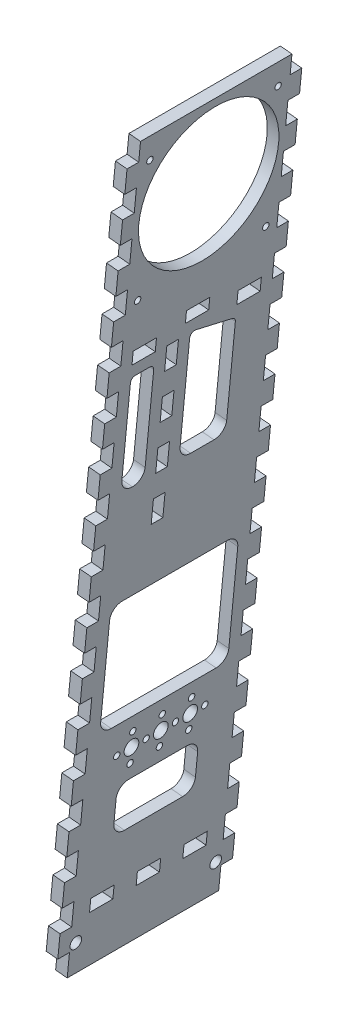
SolidWorks part; units mm, degrees
ref_plane "Front Plane" through (0, 0, 0) normal (0, 0, 1) x (1, 0, 0)
ref_plane "Top Plane" through (0, 0, 0) normal (0, 1, 0) x (1, 0, 0)
ref_plane "Right Plane" through (0, 0, 0) normal (1, 0, 0) x (0, 0, -1)
sketch "Sketch1" plane through (0, 0, 0) normal (0, 0, 1) x (1, 0, 0)
  line L0 (0, 0) -> (40.3547, 419.1) construction
  line L1 (40.3547, 419.1) -> (159.2585, 419.1) construction
  line L2 (159.2585, 419.1) -> (159.2585, 0) construction
  line L3 (159.2585, 0) -> (0, 0) construction
  line L4 (159.2585, -1000) -> (159.2585, 49000) construction
  line L5 (2.0164, 20.9415) -> (40.3547, 419.1) construction
  line L6 (2.0164, 20.9415) -> (41.8323, 17.1077) construction
  line L7 (40.3547, 419.1) -> (80.1706, 415.2662) construction
  line L8 (41.8323, 17.1077) -> (80.1706, 415.2662) construction
  line L9 (64.0085, -1000) -> (64.0085, 49000) construction
  line L10 (-42.7214, 317.5) -> (-118.5706, 324.8034) construction
  line L11 (-20.0013, 414.3375) -> (40.196, 414.3375) construction
  line L12 (-1162.1335, 304.8) -> (48837.8665, 304.8) construction
  line L13 (-120.1415, 292.1) -> (-43.9415, 292.1) construction
  line L14 (-118.5706, 324.8034) -> (-43.9415, 292.1) construction
  line L15 (-42.7214, 317.5) -> (-120.1415, 292.1) construction
  line L16 (40.196, 338.1375) -> (-20.0013, 338.1375) construction
  line L17 (-128.0517, 325.7164) -> (29.8985, 310.5075)
  line L18 (-128.0517, 325.7164) -> (-127.4431, 332.0371)
  line L19 (-127.4431, 332.0371) -> (40.3547, 419.1)
  line L20 (40.3547, 419.1) -> (108.4585, 419.1)
  line L21 (108.4585, 419.1) -> (108.4585, 0) construction
  line L22 (29.8985, 310.5075) -> (0.4102, 4.2603)
  line L23 (0.4102, 4.2603) -> (44.6556, 0)
  line L24 (44.6556, 0) -> (108.4585, 0)
  line L25 (108.4585, 419.1) -> (159.2585, 311.15)
  line L26 (159.2585, 311.15) -> (159.2585, 304.8)
  line L27 (159.2585, 304.8) -> (108.4585, 280.8941)
  line L28 (108.4585, 280.8941) -> (108.4585, 0)
  line L29 (29.9603, 304.8) -> (29.9603, 311.15) construction
  line L30 (108.4585, 38.1) -> (3.0572, 38.1)
  line L31 (108.4585, 38.1) -> (108.4585, 31.75)
  line L32 (108.4585, 31.75) -> (3.0572, 31.75)
  line L33 (3.0572, 38.1) -> (3.0572, 31.75)
  line L34 (29.9603, 311.15) -> (36.3397, 311.15) construction
  arc A0 (-118.5706, 324.8034) -> (-20.0013, 414.3375) centre (-20.0013, 315.3123) cw construction
  arc A1 (73.5335, 304.8) -> (40.196, 338.1375) centre (40.196, 304.8) ccw construction
  arc A2 (149.7335, 304.8) -> (40.196, 414.3375) centre (40.196, 304.8) ccw construction
  arc A3 (-42.7214, 317.5) -> (-20.0013, 338.1375) centre (-20.0013, 315.3123) cw construction
  point P7 (57.6585, 400.05)
  point P10 (46.2594, 414.1696)
  point P17 (149.7335, 304.8)
  point P18 (73.5335, 304.8)
  point P43 (10.048, 38.1)
  point P44 (19.5659, 203.2)
  dimension "D9" = 9.525
  dimension "D14" = 25.4
  dimension "D1" = 419.1
  dimension "D2" = 101.6
  dimension "D3" = 19.05
  dimension "D4" = 19.05
  dimension "D5" = 84.5
  dimension "D6" = 40
  dimension "D7" = 400
  dimension "D8" = 95.25
  dimension "D10" = 9.525
  dimension "D11" = 114.3
  dimension "D12" = 76.2
  dimension "D13" = 9.525
  dimension "D15" = 127
  dimension "D16" = 9.525
  dimension "D17" = 203.2
  dimension "D18" = 6.35
  dimension "D19" = 50.8
  dimension "D20" = 44.45
  dimension "D21" = 6.35
  dimension "D22" = 6.35
  dimension "D23" = 31.75
  dimension "D24" = 6.35
  dimension "D25" = 6.35
  dimension "D26" = 101.6
  dimension "D27" = 6.35
  dimension "D28" = 6.35
sketch "Sketch2" plane through (0, 0, 0) normal (0, 0, 1) x (1, 0, 0)
  line L0 (6.731, 3.6517) -> (0.4102, 4.2603)
  line L1 (6.731, 3.6517) -> (46.6755, 418.4914)
  line L2 (0.4102, 4.2603) -> (40.3547, 419.1)
  line L3 (46.6755, 418.4914) -> (40.3547, 419.1)
  line L4 (0.4102, 4.2603) -> (44.6556, 0) construction
  line L5 (40.3547, 419.1) -> (108.4585, 419.1) construction
  dimension "D2" = 6.35
extrude "Boss-Extrude1" add sketch "Sketch2" along normal blind 95.25
sketch "Sketch3" plane through (0, 0, 0) normal (-0.9954, 0.0958, 0) x (0, 0, 1)
  line L0 (47.625, 378.199) -> (47.625, 421.0384) construction
  line L1 (95.25, 421.0384) -> (0, 421.0384) construction
  line L2 (47.625, 416.6966) -> (0, 416.6966) construction
  line L3 (0, 421.0384) -> (0, 4.28) construction
  line L4 (47.625, 339.7014) -> (0, 339.7014) construction
  line L5 (0, 0) -> (0, 421.0384) construction
  ellipse E0 centre (47.625, 378.199) end of major axis (47.625, 416.6966) minor radius 38.1
  dimension "D1" = 76.2
extrude "Cut-Extrude1" cut sketch "Sketch3" against normal through all
sketch "Sketch4" plane through (0, 0, 0) normal (-0.9954, 0.0958, 0) x (0, 0, 1)
  line L0 (95.25, 4.28) -> (0, 4.28) construction
  line L1 (9.525, -11.595) -> (85.725, -11.595) construction
  line L2 (9.525, -11.595) -> (9.525, 20.155) construction
  line L3 (9.525, 20.155) -> (85.725, 20.155) construction
  line L4 (85.725, -11.595) -> (85.725, 20.155) construction
  line L5 (9.525, -11.595) -> (85.725, 20.155) construction
  line L6 (9.525, 20.155) -> (85.725, -11.595) construction
  line L7 (0, 421.0384) -> (0, 4.28) construction
  circle A0 centre (9.525, 20.155) radius 3.175
  circle A1 centre (85.725, 20.155) radius 3.175
  point P0 (47.625, 4.28)
  dimension "D3" = 6.35
  dimension "D1" = 9.525
  dimension "D2" = 15.875
extrude "Cut-Extrude2" cut sketch "Sketch4" against normal through all
sketch "Sketch5" plane through (0, 0, 0) normal (-0.9954, 0.0958, 0) x (0, 0, 1)
  line L0 (95.25, 4.28) -> (0, 4.28) construction
  line L1 (47.625, -995.72) -> (47.625, 49004.28) construction
  line L2 (63.625, 105.88) -> (63.625, 113.88) construction
  circle A0 centre (63.625, 105.88) radius 4
  circle A1 centre (63.625, 113.88) radius 1.75
  circle A2 centre (71.625, 105.88) radius 1.75
  circle A3 centre (63.625, 97.88) radius 1.75
  circle A4 centre (55.625, 105.88) radius 1.75
  point P7 (47.625, 4.28)
  point P18 (63.625, 105.88)
  dimension "D2" = 8
  dimension "D5" = 3.5
  dimension "D1" = 101.6
  dimension "D3" = 16
  dimension "D4" = 8
  dimension "D6" = 4
extrude "Cut-Extrude3" cut sketch "Sketch5" against normal through all
pattern_linear "LPattern1" count 3 spacing 16 along (0, 0, -1) of "Cut-Extrude3"
sketch "Sketch6" plane through (0, 0, 0) normal (-0.9954, 0.0958, 0) x (0, 0, 1)
  line L0 (0, 421.0384) -> (0, 4.28) construction
  line L1 (12.7, 185.38) -> (82.55, 185.38)
  line L2 (12.7, 185.38) -> (12.7, 121.88)
  line L3 (12.7, 121.88) -> (82.55, 121.88)
  line L4 (82.55, 185.38) -> (82.55, 121.88)
  line L5 (95.25, 421.0384) -> (95.25, 4.28) construction
  circle A0 centre (63.625, 105.88) radius 4 construction
  dimension "D1" = 12.7
  dimension "D2" = 12.7
  dimension "D3" = 16
  dimension "D4" = 63.5
extrude "Cut-Extrude4" cut sketch "Sketch6" against normal through all
sketch "Sketch7" plane through (0, 0, 0) normal (-0.9954, 0.0958, 0) x (0, 0, 1)
  line L0 (0, 421.0384) -> (0, 4.28) construction
  line L1 (25.4, 89.88) -> (69.85, 89.88)
  line L2 (25.4, 89.88) -> (25.4, 64.48)
  line L3 (25.4, 64.48) -> (69.85, 64.48)
  line L4 (69.85, 89.88) -> (69.85, 64.48)
  line L5 (95.25, 421.0384) -> (95.25, 4.28) construction
  circle A0 centre (63.625, 105.88) radius 4 construction
  dimension "D1" = 25.4
  dimension "D2" = 25.4
  dimension "D3" = 16
  dimension "D4" = 25.4
extrude "Cut-Extrude5" cut sketch "Sketch7" against normal through all
sketch "Sketch8" plane through (0, 0, 0) normal (-0.9954, 0.0958, 0) x (0, 0, 1)
  line L0 (0, 421.0384) -> (0, 4.28) construction
  line L1 (0, 16.98) -> (6.35, 16.98)
  line L2 (0, 16.98) -> (0, 4.28)
  line L3 (0, 4.28) -> (6.35, 4.28)
  line L4 (6.35, 16.98) -> (6.35, 4.28)
  line L5 (95.25, 4.28) -> (0, 4.28) construction
  line L6 (95.25, 421.0384) -> (95.25, 4.28) construction
  line L7 (95.25, 16.98) -> (88.9, 16.98)
  line L8 (95.25, 16.98) -> (95.25, 4.28)
  line L9 (95.25, 4.28) -> (88.9, 4.28)
  line L10 (88.9, 16.98) -> (88.9, 4.28)
  dimension "D1" = 12.7
  dimension "D2" = 6.35
extrude "Cut-Extrude6" cut sketch "Sketch8" against normal through all
pattern_linear "LPattern2" count 17 spacing 25.4 along (0.0958, 0.9954, 0) of "Cut-Extrude6"
sketch "Sketch9" plane through (0, 0, 0) normal (-0.9954, 0.0958, 0) x (0, 0, 1)
  line L0 (47.625, 38.8877) -> (47.625, 64.48) construction
  line L1 (15.875, 38.8877) -> (28.575, 38.8877)
  line L2 (15.875, 38.8877) -> (15.875, 31.8968)
  line L3 (15.875, 31.8968) -> (28.575, 31.8968)
  line L4 (28.575, 38.8877) -> (28.575, 31.8968)
  line L5 (41.275, 38.8877) -> (53.975, 38.8877)
  line L6 (41.275, 38.8877) -> (41.275, 31.8968)
  line L7 (41.275, 31.8968) -> (53.975, 31.8968)
  line L8 (53.975, 38.8877) -> (53.975, 31.8968)
  line L9 (79.375, 38.8877) -> (66.675, 38.8877)
  line L10 (79.375, 38.8877) -> (79.375, 31.8968)
  line L11 (79.375, 31.8968) -> (66.675, 31.8968)
  line L12 (66.675, 38.8877) -> (66.675, 31.8968)
  line L13 (25.4, 64.48) -> (69.85, 64.48) construction
  dimension "D1" = 12.7
  dimension "D2" = 12.7
  dimension "D3" = 12.7
extrude "Cut-Extrude7" cut sketch "Sketch9" against normal through all
sketch "Sketch10" plane through (0, 0, 0) normal (-0.9954, 0.0958, 0) x (0, 0, 1)
  line L0 (47.625, 373.4134) -> (47.625, 421.0384) construction
  line L1 (82.55, 338.4884) -> (12.7, 338.4884) construction
  line L2 (82.55, 338.4884) -> (82.55, 408.3384) construction
  line L3 (82.55, 408.3384) -> (12.7, 408.3384) construction
  line L4 (12.7, 338.4884) -> (12.7, 408.3384) construction
  line L5 (82.55, 338.4884) -> (12.7, 408.3384) construction
  line L6 (82.55, 408.3384) -> (12.7, 338.4884) construction
  line L7 (88.9, 421.0384) -> (6.35, 421.0384) construction
  circle A0 centre (12.7, 408.3384) radius 1.75
  circle A1 centre (82.55, 408.3384) radius 1.75
  circle A2 centre (82.55, 338.4884) radius 1.75
  circle A3 centre (12.7, 338.4884) radius 1.75
  point P0 (47.625, 373.4134)
  dimension "D4" = 3.5
  dimension "D1" = 69.85
  dimension "D2" = 82.55
  dimension "D3" = 12.7
extrude "Cut-Extrude8" cut sketch "Sketch10" against normal through all
sketch "Sketch11" plane through (0, 0, 0) normal (-0.9954, 0.0958, 0) x (0, 0, 1)
  line L0 (95.25, 283.68) -> (95.25, 270.98) construction
  line L1 (57.15, 229.5398) -> (63.5, 229.5398)
  line L2 (57.15, 229.5398) -> (57.15, 216.8398)
  line L3 (57.15, 216.8398) -> (63.5, 216.8398)
  line L4 (63.5, 229.5398) -> (63.5, 216.8398)
  line L5 (0, 204.1398) -> (57.15, 216.8398) construction
  line L6 (0, 207.48) -> (0, 194.78) construction
  line L8 (0, 204.1398) -> (57.15, 204.1398) construction
  line L9 (57.15, 204.1398) -> (57.15, 216.8398) construction
  dimension "D1" = 12.7
  dimension "D2" = 6.35
  dimension "D3" = 31.75
  dimension "D4" = 12.7
extrude "Cut-Extrude9" cut sketch "Sketch11" against normal through all
pattern_linear "LPattern3" count 4 spacing 25.4 along (0.0958, 0.9954, 0) of "Cut-Extrude9"
sketch "Sketch12" plane through (0, 0, 0) normal (-0.9954, 0.0958, 0) x (0, 0, 1)
  line L0 (47.625, 318.2936) -> (47.625, 421.0384) construction
  line L1 (41.275, 318.2936) -> (53.975, 318.2936)
  line L2 (41.275, 318.2936) -> (41.275, 311.9436)
  line L3 (41.275, 311.9436) -> (53.975, 311.9436)
  line L4 (53.975, 318.2936) -> (53.975, 311.9436)
  line L5 (88.9, 421.0384) -> (6.35, 421.0384) construction
  dimension "D1" = 12.7
  dimension "D2" = 6.35
extrude "Cut-Extrude10" cut sketch "Sketch12" against normal through all
sketch "Sketch13" plane through (0, 0, 0) normal (-0.9954, 0.0958, 0) x (0, 0, 1)
  line L0 (0, 311.9436) -> (0, 4.28) construction
  line L1 (12.7, 313.2005) -> (25.4, 313.2005)
  line L2 (12.7, 313.2005) -> (12.7, 306.2097)
  line L3 (12.7, 306.2097) -> (25.4, 306.2097)
  line L4 (25.4, 313.2005) -> (25.4, 306.2097)
  line L5 (69.85, 313.2005) -> (82.55, 313.2005)
  line L6 (69.85, 313.2005) -> (69.85, 306.2097)
  line L7 (69.85, 306.2097) -> (82.55, 306.2097)
  line L8 (82.55, 313.2005) -> (82.55, 306.2097)
  line L9 (95.25, 309.08) -> (95.25, 296.38) construction
  line L10 (0, 306.2097) -> (12.7, 306.2097) construction
  dimension "D1" = 12.7
  dimension "D2" = 12.7
  dimension "D3" = 12.7
extrude "Cut-Extrude11" cut sketch "Sketch13" against normal through all
sketch "Sketch14" plane through (0, 0, 0) normal (-0.9954, 0.0958, 0) x (0, 0, 1)
  line L0 (57.15, 254.9398) -> (57.15, 242.2398) construction
  line L1 (69.85, 242.2398) -> (82.55, 242.2398)
  line L2 (69.85, 242.2398) -> (69.85, 299.8597)
  line L3 (69.85, 299.8597) -> (82.55, 299.8597)
  line L4 (82.55, 242.2398) -> (82.55, 299.8597)
  line L5 (50.8, 242.2398) -> (25.4, 242.2398)
  line L6 (50.8, 242.2398) -> (50.8, 299.8597)
  line L7 (50.8, 299.8597) -> (25.4, 299.8597) construction
  line L8 (25.4, 242.2398) -> (25.4, 299.8597)
  line L9 (63.5, 242.2398) -> (63.5, 254.9398) construction
  line L10 (88.9, 270.98) -> (88.9, 258.28) construction
  line L11 (57.15, 242.2398) -> (63.5, 242.2398) construction
  line L12 (69.85, 306.2097) -> (82.55, 306.2097) construction
  line L13 (25.4, 299.8597) -> (50.8, 306.2097)
  line L14 (50.8, 306.2097) -> (50.8, 299.8597)
  dimension "D1" = 6.35
  dimension "D2" = 6.35
  dimension "D3" = 6.35
  dimension "D4" = 6.35
  dimension "D5" = 25.4
extrude "Cut-Extrude12" cut sketch "Sketch14" against normal through all
fillet "Fillet1" radius 6.35 8 edges at (9.3405, 63.8789, 25.4) (11.775, 89.1619, 25.4) (11.775, 89.1619, 69.85) (9.3405, 63.8789, 69.85) (14.8421, 121.0146, 82.55) (20.9283, 184.2223, 82.55) (20.9283, 184.2223, 12.7) (14.8421, 121.0146, 12.7)
fillet "Fillet2" radius 6.35 4 edges at (26.378, 240.8203, 69.85) (26.378, 240.8203, 82.55) (26.378, 240.8203, 50.8) (26.378, 240.8203, 25.4)
fillet "Fillet3" radius 2.54 4 edges at (31.9007, 298.1749, 82.55) (32.5093, 304.4957, 50.8) (31.9007, 298.1749, 25.4) (31.9007, 298.1749, 69.85)
